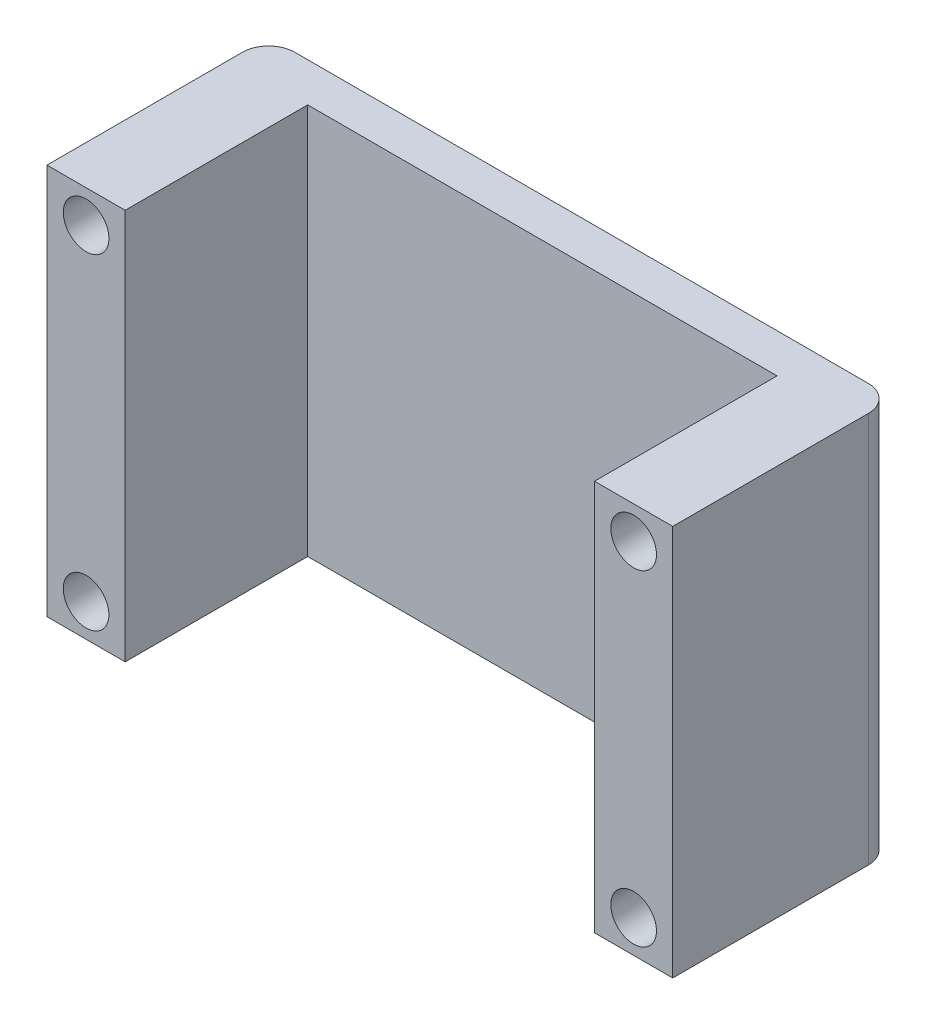
SolidWorks part; units mm, degrees
other "Marca1"
sketch "Croquis2" plane through (24, 2.5, 3) normal (0.0063, 0.5718, 0.8204) x (1, 0, -0.0077)
ref_plane "Alzado" through (0, 0, 0) normal (0, 0, 1) x (1, 0, 0)
ref_plane "Planta" through (0, 0, 0) normal (0, 1, 0) x (1, 0, 0)
ref_plane "Vista lateral" through (0, 0, 0) normal (1, 0, 0) x (0, 0, -1)
sketch "Croquis1" plane through (0, 0, 0) normal (0, 0, 1) x (1, 0, 0)
  line L0 (21, 0) -> (-21, 0) construction
  line L1 (24, -2.5) -> (-24, -2.5)
  line L2 (24, -2.5) -> (24, 2.5)
  line L4 (-24, -2.5) -> (-24, 2.5)
  line L5 (24, -2.5) -> (-24, 2.5) construction
  line L6 (24, 2.5) -> (-24, -2.5) construction
  line L7 (24, 22.5) -> (-24, 27.5) construction
  line L9 (-24, 2.5) -> (-24, 22.5)
  line L10 (-24, 12.5) -> (24, 12.5)
  line L11 (24, 2.5) -> (24, 22.5)
  line L12 (24, 27.5) -> (-24, 22.5) construction
  line L13 (21, 25) -> (-21, 25) construction
  line L14 (-24, 27.5) -> (-24, 22.5)
  line L15 (24, 27.5) -> (24, 22.5)
  line L16 (24, 27.5) -> (-24, 27.5)
  circle A0 centre (-21, 0) radius 1.75
  circle A1 centre (21, 0) radius 1.75
  circle A2 centre (21, 25) radius 1.75
  circle A3 centre (-21, 25) radius 1.75
  point P0 (0, 0)
  point P9 (0, 0)
  point P13 (-27.7302, 12.8897)
  point P14 (0, 0)
  point P23 (0, 25)
  dimension "D3" = 3.5
  dimension "D1" = 48
  dimension "D2" = 5
  dimension "D4" = 42
  dimension "D5" = 15
extrude "Saliente-Extruir1" add sketch "Croquis1" along normal blind 3 contours L15 L16 L14 L9 L10 L11 A2 A3 | L2 L11 L10 L9 L4 L1 A1 A0
sketch "Croquis3" plane through (0, 0, 3) normal (0, 0, 1) x (1, 0, 0)
  line L17 (-24, 27.5) -> (-18, 27.5)
  line L18 (-24, 27.5) -> (-24, -2.5)
  line L19 (-24, -2.5) -> (-18, -2.5)
  line L20 (24, -2.5) -> (24, 27.5)
  line L21 (24, 27.5) -> (-24, 27.5)
  line L22 (-24, 27.5) -> (-24, -2.5)
  line L23 (-24, -2.5) -> (24, -2.5)
  line L24 (24, -2.5) -> (24, 27.5)
  line L25 (24, 27.5) -> (-24, 27.5)
  line L26 (-24, 27.5) -> (-24, -2.5)
  line L27 (-24, -2.5) -> (24, -2.5)
  line L28 (-18, 27.5) -> (-18, -2.5)
  line L29 (24, 27.5) -> (18, 27.5)
  line L30 (24, 27.5) -> (24, -2.5)
  line L31 (24, -2.5) -> (18, -2.5)
  line L32 (18, 27.5) -> (18, -2.5)
  circle A4 centre (21, 25) radius 1.75 construction
  circle A5 centre (21, 0) radius 1.75 construction
  circle A16 centre (-21, 0) radius 1.75 construction
  circle A17 centre (-21, 25) radius 1.75 construction
  circle A18 centre (21, 25) radius 1.75
  circle A19 centre (21, 0) radius 1.75
  circle A20 centre (-21, 0) radius 1.75
  circle A21 centre (-21, 25) radius 1.75
  dimension "D2" = 6
  dimension "D1" = 0
extrude "Saliente-Extruir4" add sketch "Croquis3" along normal blind 14
fillet "Redondeo1" radius 2 2 edges at (24, 12.5, 0) (-24, 12.5, 0)
